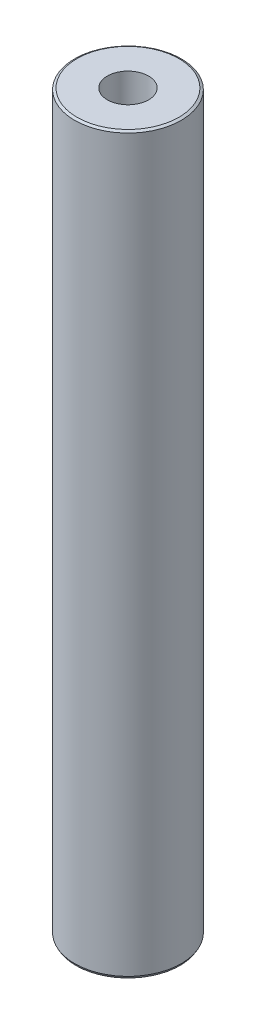
SolidWorks part; units mm, degrees
ref_plane "Front Plane" through (0, 0, 0) normal (0, 0, 1) x (1, 0, 0)
ref_plane "Top Plane" through (0, 0, 0) normal (0, 1, 0) x (1, 0, 0)
ref_plane "Right Plane" through (0, 0, 0) normal (1, 0, 0) x (0, 0, -1)
sketch "Sketch1" plane through (0, 0, 0) normal (0, 1, 0) x (1, 0, 0)
  circle A0 centre (0, 0) radius 22.5
  dimension "SHAFT_OD" = 45
extrude "Boss-Extrude1" add sketch "Sketch1" along normal blind 309.7394
sketch "Sketch2" plane through (0, 0, 0) normal (0, 1, 0) x (1, 0, 0)
  circle A0 centre (0, 0) radius 8.7185
  dimension "BORE_D" = 17.437
extrude "Cut-Extrude1" cut sketch "Sketch2" along normal through all
chamfer "Chamfer1" distance 0.59 angle 60 2 edges at (0, 309.7394, 22.5) (0, 0, 22.5) first distance on face at (0, 309.7394, 22.5) first distance on face at (0, 0, 8.7185)
